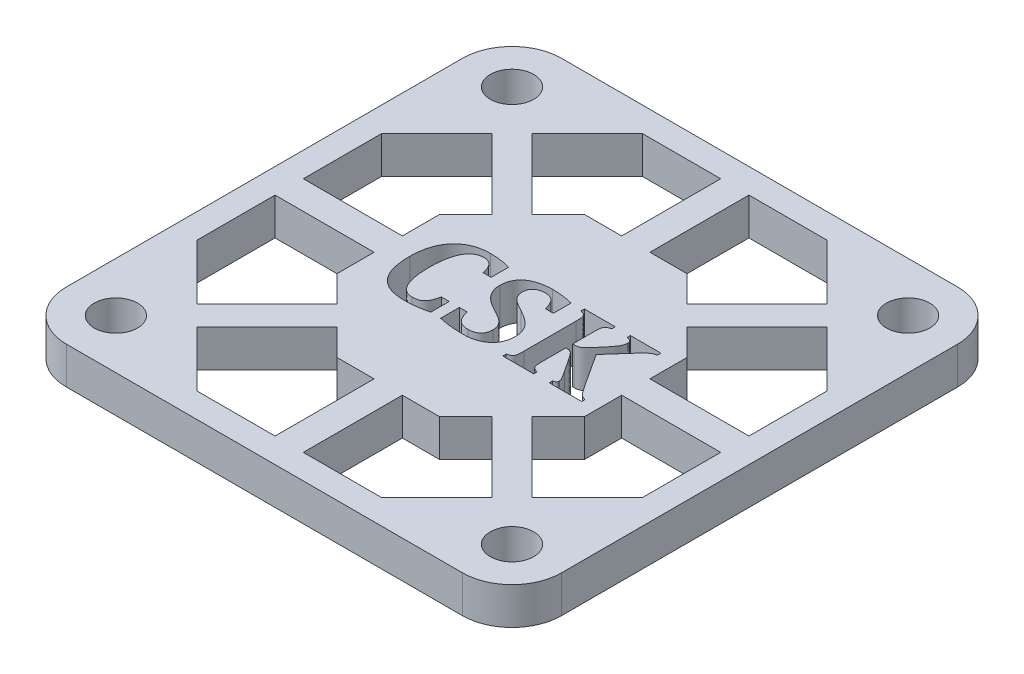
SolidWorks part; units mm, degrees
ref_plane "Front Plane" through (0, 0, 0) normal (0, 0, 1) x (1, 0, 0)
ref_plane "Top Plane" through (0, 0, 0) normal (0, 1, 0) x (1, 0, 0)
ref_plane "Right Plane" through (0, 0, 0) normal (1, 0, 0) x (0, 0, -1)
sketch "Sketch1" plane through (0, 0, 0) normal (0, 1, 0) x (1, 0, 0)
  line L1 (0, 0) -> (40, 0)
  line L2 (0, 0) -> (0, 40)
  line L3 (0, 40) -> (40, 40)
  line L4 (40, 0) -> (40, 40)
  dimension "D1" = 40
extrude "Boss-Extrude1" add sketch "Sketch1" along normal blind 3
sketch "Sketch2" plane through (0, 3, 0) normal (0, 1, 0) x (1, 0, 0)
  line L0 (4, 36) -> (36, 4) construction
  line L1 (4, 4) -> (36, 36) construction
  line L2 (20, 0) -> (20, 40) construction
  line L3 (0, 0) -> (40, 0) construction
  line L4 (40, 40) -> (0, 40) construction
  circle A0 centre (4, 4) radius 1.75
  circle A1 centre (36, 4) radius 1.75
  circle A2 centre (36, 36) radius 1.75
  circle A3 centre (4, 36) radius 1.75
  point P8 (20, 20)
  dimension "D1" = 3.5
  dimension "D2" = 32
extrude "Cut-Extrude1" cut sketch "Sketch2" against normal through all
fillet "Fillet1" radius 4 4 edges at (40, 1.5, -40) (0, 1.5, -40) (40, 1.5, 0) (0, 1.5, 0)
sketch "Sketch4" plane through (0, 3, 0) normal (0, 1, 0) x (1, 0, 0)
  line L0 (20, 40) -> (20, 0) construction
  line L1 (36, 40) -> (4, 40) construction
  line L2 (4, 0) -> (36, 0) construction
  line L3 (0, 20) -> (40, 20) construction
  line L4 (0, 36) -> (0, 4) construction
  line L5 (40, 4) -> (40, 36) construction
  line L6 (38, 27.4558) -> (27.4558, 38) construction
  line L7 (30, 24.1421) -> (24.1421, 30) construction
  line L8 (24.1421, 30) -> (15.8579, 30) construction
  line L9 (15.8579, 30) -> (10, 24.1421) construction
  line L10 (10, 24.1421) -> (10, 15.8579) construction
  line L11 (10, 15.8579) -> (15.8579, 10) construction
  line L12 (15.8579, 10) -> (24.1421, 10) construction
  line L13 (24.1421, 10) -> (30, 15.8579) construction
  line L14 (30, 15.8579) -> (30, 24.1421) construction
  line L15 (27.4558, 38) -> (12.5442, 38) construction
  line L16 (12.5442, 38) -> (2, 27.4558) construction
  line L17 (2, 27.4558) -> (2, 12.5442) construction
  line L18 (2, 12.5442) -> (12.5442, 2) construction
  line L19 (12.5442, 2) -> (27.4558, 2) construction
  line L20 (27.4558, 2) -> (38, 12.5442) construction
  line L21 (38, 12.5442) -> (38, 27.4558) construction
  line L22 (26.2635, 27.8787) -> (31.9203, 33.5355)
  line L23 (21.1421, 30) -> (21.1421, 38)
  line L24 (26.2635, 27.8787) -> (24.1421, 30)
  line L25 (24.1421, 30) -> (21.1421, 30)
  line L26 (31.9203, 33.5355) -> (27.4558, 38)
  line L27 (27.4558, 38) -> (21.1421, 38)
  circle A0 centre (20, 20) radius 10 construction
  dimension "D1" = 20
  dimension "D3" = 3
  dimension "D4" = 3
  dimension "D2" = 8
extrude "Cut-Extrude2" cut sketch "Sketch4" against normal through all
ref_plane "Plane1" through (0, 0, -20) normal (0, 0, 1) x (1, 0, 0)
ref_plane "Plane2" through (20, 0, 0) normal (1, 0, 0) x (0, 0, -1)
ref_axis "Axis1" through (20, 3.15, -20) along (0, -1, 0)
pattern_circular "CirPattern1" count 8 over 360 about axis through (20, 3.15, -20) along (0, -1, 0) of "Cut-Extrude2"
sketch "Sketch5" plane through (0, 3, 0) normal (0, 1, 0) x (1, 0, 0)
  line L0 (10, 16.8) -> (30, 16.8) construction
  line L1 (10, 15.8579) -> (10, 18.8579) construction
  line L2 (30, 18.8579) -> (30, 15.8579) construction
  line L3 (18.8579, 10) -> (15.8579, 10) construction
  text T0 "CSK" font "Cambria" height in points 24
  dimension "D1" = 6.8
extrude "Cut-Extrude3" cut sketch "Sketch5" against normal through all
